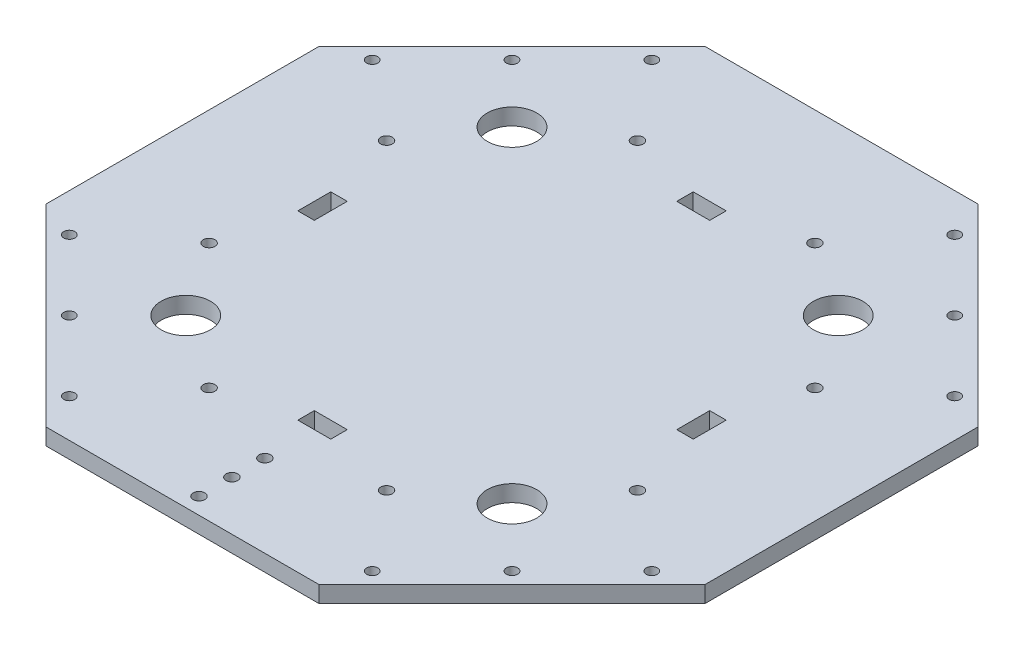
SolidWorks part; units mm, degrees
material "Custom Plastic"
ref_plane "Front Plane" through (0, 0, 0) normal (0, 0, 1) x (1, 0, 0)
ref_plane "Top Plane" through (0, 0, 0) normal (0, 1, 0) x (1, 0, 0)
ref_plane "Right Plane" through (0, 0, 0) normal (1, 0, 0) x (0, 0, -1)
ref_axis "Axis1" through (0, -0.2997, 0) along (0, 1, 0)
sketch "Base sketch" plane through (0, 0, 0) normal (0, 1, 0) x (1, 0, 0)
  line L1 (-127, 52.6051) -> (-127, -52.6051)
  line L2 (-127, -52.6051) -> (-52.6051, -127)
  line L3 (-52.6051, -127) -> (52.6051, -127)
  line L4 (52.6051, -127) -> (127, -52.6051)
  line L5 (127, -52.6051) -> (127, 52.6051)
  line L6 (127, 52.6051) -> (52.6051, 127)
  line L7 (52.6051, 127) -> (-52.6051, 127)
  line L8 (-52.6051, 127) -> (-127, 52.6051)
  circle A0 centre (0, 0) radius 127 construction
  dimension "D1" = 254
extrude "Base" add sketch "Base sketch" along normal blind 6.35
sketch "Sketch3" plane through (0, 6.35, 0) normal (0, 1, 0) x (1, 0, 0)
  line L0 (52.6051, 127) -> (-52.6051, 127) construction
  line L1 (-34.925, 114.3) -> (34.925, 114.3)
  line L2 (-34.925, 114.3) -> (-34.925, 79.375)
  line L4 (-34.925, 79.375) -> (34.925, 79.375)
  line L5 (34.925, 114.3) -> (34.925, 79.375)
  point P6 (0, 79.375)
  dimension "D1" = 69.85
  dimension "D2" = 34.925
  dimension "D3" = 12.7
sketch "Sketch4" plane through (0, 6.35, 0) normal (0, 1, 0) x (1, 0, 0)
  line L0 (0, 0) -> (0, 127) construction
  line L1 (52.6051, 127) -> (-52.6051, 127) construction
  line L4 (-6.35, 69.85) -> (6.35, 69.85)
  line L5 (-6.35, 69.85) -> (-6.35, 76.2)
  line L6 (-6.35, 76.2) -> (6.35, 76.2)
  line L7 (6.35, 69.85) -> (6.35, 76.2)
  line L8 (-6.35, 69.85) -> (6.35, 76.2) construction
  line L10 (-6.35, 76.2) -> (6.35, 69.85) construction
  point P5 (0, 73.025)
  dimension "D1" = 6.35
  dimension "D2" = 12.7
  dimension "D3" = 53.975
extrude "Support cutouts" cut sketch "Sketch4" against normal up to next
pattern_circular "Support cutout pattern" count 4 over 360 about axis through (0, -0.2997, 0) along (0, 1, 0) of "Support cutouts"
sketch "Sketch11" plane through (0, 6.35, 0) normal (0, 1, 0) x (1, 0, 0)
  line L1 (95.25, 39.4538) -> (39.4538, 95.25) construction
  line L2 (39.4538, 95.25) -> (-39.4538, 95.25) construction
  line L3 (-39.4538, 95.25) -> (-95.25, 39.4538) construction
  line L4 (-95.25, 39.4538) -> (-95.25, -39.4538) construction
  line L5 (-95.25, -39.4538) -> (-39.4538, -95.25) construction
  line L6 (-39.4538, -95.25) -> (39.4538, -95.25) construction
  line L7 (39.4538, -95.25) -> (95.25, -39.4538) construction
  line L8 (95.25, -39.4538) -> (95.25, 39.4538) construction
  line L9 (-34.1933, 82.55) -> (-82.55, 34.1933)
  line L10 (-82.55, 34.1933) -> (-82.55, -34.1933)
  line L11 (-82.55, -34.1933) -> (-34.1933, -82.55)
  line L12 (-34.1933, -82.55) -> (34.1933, -82.55)
  line L13 (34.1933, -82.55) -> (82.55, -34.1933)
  line L14 (82.55, -34.1933) -> (82.55, 34.1933)
  line L15 (82.55, 34.1933) -> (34.1933, 82.55)
  line L16 (34.1933, 82.55) -> (-34.1933, 82.55)
  circle A0 centre (0, 0) radius 95.25 construction
  circle A1 centre (0, 0) radius 82.55 construction
  dimension "D1" = 190.5
  dimension "D2" = 12.7
hole_wizard "#8 Clearance Hole1" positions "Sketch13" profile "Sketch12" hole size "#8" standard "ANSI Inch" end condition through all
sketch "Sketch13" plane through (0, 6.35, 0) normal (0, 1, 0) x (1, 0, 0)
  point P0 (-82.55, 34.1933)
  point P3 (-34.1933, 82.55)
  point P6 (34.1933, 82.55)
  point P9 (82.55, 34.1933)
  point P12 (82.55, -34.1933)
  point P15 (34.1933, -82.55)
  point P18 (-34.1933, -82.55)
  point P21 (-82.55, -34.1933)
sketch "Sketch12" plane through (-82.55, 6.35, -34.1933) normal (1, 0, 0) x (0, 0, 1)
  line L0 (0, 0) -> (0, 6.35)
  line L1 (0, 6.35) -> (2.2479, 6.35)
  line L2 (2.2479, 6.35) -> (2.2479, 0)
  line L5 (2.2479, 0) -> (0, 0)
  line L11 (0, -6.35) -> (0, 107.95) construction
  dimension "Thru Hole Dia." = 4.4958
  dimension "Thru Hole Depth" = 6.35
sketch "Sketch14" plane through (0, 6.35, 0) normal (0, 1, 0) x (1, 0, 0)
  circle A0 centre (-62.8618, 62.8618) radius 9.525
  circle A1 centre (62.8618, 62.8618) radius 9.525
  circle A2 centre (62.8618, -62.8618) radius 9.525
  circle A3 centre (-62.8618, -62.8618) radius 9.525
  point P13 (0, 0)
  dimension "D2" = 19.05
  dimension "D1" = 88.9
  dimension "D3" = 4
extrude "Cable holes" cut sketch "Sketch14" against normal up to next
sketch "Sketch15" plane through (0, 6.35, 0) normal (0, 1, 0) x (1, 0, 0)
  line L0 (0, -127) -> (0, 0) construction
  line L1 (-52.6051, -127) -> (52.6051, -127) construction
  point P5 (0, -120.65)
  point P6 (0, -107.95)
  point P7 (0, -95.25)
  dimension "D1" = 6.35
  dimension "D2" = 12.7
  dimension "D3" = 12.7
hole_wizard "#8 Clearance Hole2" positions "Sketch17" profile "Sketch16" hole size "#8" standard "ANSI Inch" end condition through all
sketch "Sketch17" plane through (0, 6.35, 0) normal (0, 1, 0) x (1, 0, 0)
  point P0 (0, -120.65)
  point P3 (0, -107.95)
  point P6 (0, -95.25)
sketch "Sketch16" plane through (0, 6.35, 120.65) normal (1, 0, 0) x (0, 0, 1)
  line L0 (0, 0) -> (0, 6.35)
  line L1 (0, 6.35) -> (2.2479, 6.35)
  line L2 (2.2479, 6.35) -> (2.2479, 0)
  line L5 (2.2479, 0) -> (0, 0)
  line L11 (0, -6.35) -> (0, 107.95) construction
  dimension "Thru Hole Dia." = 4.4958
  dimension "Thru Hole Depth" = 6.35
sketch "Sketch18" plane through (0, 6.35, 0) normal (0, 1, 0) x (1, 0, 0)
  line L0 (89.8026, 89.8026) -> (0, 0) construction
  line L1 (127, 52.6051) -> (52.6051, 127) construction
  line L2 (58.3717, 112.2532) -> (112.2532, 58.3717) construction
  point P7 (85.3124, 85.3124)
  dimension "D1" = 76.2
  dimension "D2" = 6.35
hole_wizard "plate mounting holes" positions "Sketch20" profile "Sketch19" hole size "#8" standard "ANSI Inch"
sketch "Sketch20" plane through (0, 6.35, 0) normal (0, 1, 0) x (1, 0, 0)
  line L0 (58.3717, 112.2532) -> (112.2532, 58.3717) construction
  point P0 (112.2532, 58.3717)
  point P3 (85.3124, 85.3124)
  point P7 (58.3717, 112.2532)
sketch "Sketch19" plane through (112.2532, 6.35, -58.3717) normal (1, 0, 0) x (0, 0, 1)
  line L0 (0, 0) -> (0, 6.351)
  line L1 (0, 6.351) -> (2.1526, 6.351)
  line L2 (2.1526, 6.351) -> (2.1526, 0)
  line L5 (2.1526, 0) -> (0, 0)
  line L10 (0, 6.351) -> (-2.1527, 6.351) construction
  line L11 (0, -6.35) -> (0, 107.95) construction
  dimension "Hole Dia." = 4.3053
  dimension "Hole Depth" = 6.351
  dimension "Drill Angle" = 180
pattern_circular "CirPattern1" count 4 over 360 about axis through (0, -0.2997, 0) along (0, 1, 0) of "plate mounting holes"
equation "\"MAT_THICKNESS\"=0.25"
equation "\"D1@Base\"=\"MAT_THICKNESS\""
equation "\"D1@Sketch4\"=\"MAT_THICKNESS\""
